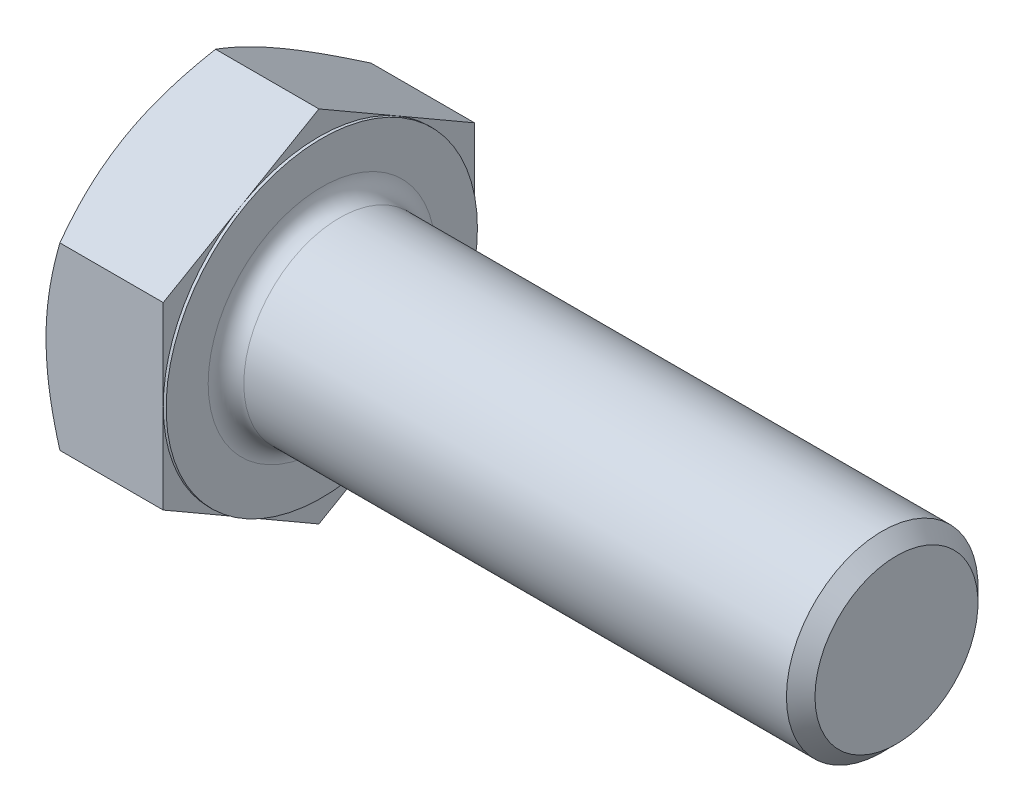
SolidWorks part; units mm, degrees
extrude "BaseHead" add sketch "Sketch1" along normal blind 15.9258
sketch "Sketch1" plane through (0, 0, 0) normal (1, 0, 0) x (0, 0, -1)
  line L0 (20.6375, 11.9151) -> (20.6375, -11.9151)
  line L1 (-20.6375, 11.9151) -> (-20.6375, -11.9151)
  line L2 (20.6375, -11.9151) -> (0, -23.8301)
  line L3 (0, -23.8301) -> (-20.6375, -11.9151)
  line L4 (20.6375, 11.9151) -> (0, 23.8301)
  line L5 (0, 23.8301) -> (-20.6375, 11.9151)
  dimension "D2" = 120
  dimension "D3" = 20.6375
  dimension "D4" = 20.6375
  dimension "D5" = 20.6375
revolve "HeadChamfer" cut sketch "Sketch3" angle 360 about L6 other way angle 60
sketch "Sketch3" plane through (0, 0, 0) normal (0, 0, 1) x (1, 0, 0)
  line L0 (0, 20.6375) -> (5.5094, 30.1801)
  line L1 (0, 23.8301) -> (0, 11.9151) construction
  line L2 (5.5094, 30.1801) -> (5.5094, 36.5301)
  line L3 (5.5094, 36.5301) -> (-12.7, 36.5301)
  line L4 (-12.7, 36.5301) -> (-12.7, 20.6375)
  line L5 (-12.7, 20.6375) -> (0, 20.6375)
  line L6 (0, 0) -> (99.06, 0) construction
  line L7 (15.9258, 23.8301) -> (0, 23.8301) construction
  dimension "D1" = 20.6375
  dimension "D2" = 6.35
  dimension "D3" = 12.7
  dimension "D4" = 6.35
  dimension "Head_ch_ang" = 30
ref_plane "Plane1" through (0, 0, 0) normal (0, 0, 1) x (1, 0, 0)
ref_plane "Plane2" through (0, 0, 0) normal (0, 1, 0) x (1, 0, 0)
ref_plane "Plane3" through (0, 0, 0) normal (1, 0, 0) x (0, 0, -1)
sketch "BodySke" plane through (0, 0, 0) normal (0, 0, 1) x (1, 0, 0)
  line L0 (0, 11.9151) -> (0, -11.9151) construction
  line L1 (0, 0) -> (92.1258, 0)
  line L2 (0, 0) -> (0, 12.7)
  line L3 (0, 12.7) -> (90.2335, 12.7)
  line L4 (92.1258, 0) -> (92.1258, 10.8077)
  line L5 (15.9258, 23.8301) -> (15.9258, 11.9151) construction
  line L6 (92.1258, 10.8077) -> (90.2335, 12.7)
  line L7 (0, 0) -> (96.52, 0) construction
  line L8 (92.1258, -10.8077) -> (90.2335, -12.7) construction
  line L9 (0, -12.7) -> (90.2335, -12.7) construction
  line L10 (18.034, 15.24) -> (18.034, -1.27) construction
  line L11 (60.3758, 15.24) -> (60.3758, -1.27) construction
  line L12 (15.9258, 11.9151) -> (15.9258, -11.9151) construction
  dimension "Diameter" = 25.4
revolve "BaseBody" add sketch "BodySke" angle 360 about L7
cosmetic thread "ThreadCosmetic" [suppressed] parameters "Thread_length"=31.75, "Thread_minor"=21.6154
sketch "Sketch4" plane through (0, 0, 0) normal (0, 0, 1) x (1, 0, 0)
  line L1 (15.9258, 23.8301) -> (15.9258, 11.9151) construction
  line L2 (15.9258, 20.6375) -> (15.5448, 20.6375)
  line L3 (15.9258, 20.6375) -> (15.9258, 49.2301)
  line L4 (15.9258, 49.2301) -> (15.5448, 49.2301)
  line L5 (0, 0) -> (95.25, 0) construction
  line L6 (0, 0) -> (96.52, 0) construction
  line L7 (15.5448, 20.6375) -> (15.5448, 49.2301)
  line L8 (15.9258, 23.8301) -> (1.8433, 23.8301) construction
  dimension "D1" = 20.6375
  dimension "D2" = 25.4
revolve "BearingFace" cut sketch "Sketch4" angle 360 about L5
fillet "HeadFillet" radius 2.3622 1 edges at (15.9258, 0, -12.7)
sketch "ThdSchSke" plane through (0, 0, 0) normal (0, 0, 1) x (1, 0, 0)
  line L0 (60.3758, -10.8077) -> (59.0508, -12.7)
  line L1 (60.3758, -10.8077) -> (61.7008, -12.7)
  line L2 (61.7008, -12.7) -> (61.7008, -15.875)
  line L3 (-3.175, 0) -> (5.1513, 0) construction
  line L5 (61.7008, -15.875) -> (59.0508, -15.875)
  line L6 (59.0508, -15.875) -> (59.0508, -12.7)
  dimension "Thread_minor" = 21.6154
  dimension "Diameter" = 25.4
  dimension "Start" = 60.3758
revolve "ThreadSchematic" [suppressed] cut sketch "ThdSchSke" angle 360 about L3
pattern_linear "ThdSchPat" [suppressed]
equation "\"D3@Sketch1\" = \"Width_flats@Sketch1\" / 2"
equation "\"D4@Sketch1\" = \"D3@Sketch1\""
equation "\"D5@Sketch1\" = \"D4@Sketch1\""
equation "\"Thread_minor@ThreadCosmetic\" = \"Minor_dia@BodySke\""
equation "\"D1@Sketch3\" = \"Width_flats@Sketch1\" / 2"
equation "\"D1@Sketch4\" = \"Width_flats@Sketch1\" / 2"
equation "\"Thread_length@ThreadCosmetic\" = ((sgn( (\"Length@BodySke\" - \"Advance@BodySke\" ) - \"Thread_nom@BodySke\" )-1)*( (\"Length@BodySke\" - \"Advance@BodySke\" ) - \"Thread_nom@BodySke\" ))/-2+ \"Thread_nom@BodySke\""
equation "\"Thread_minor@ThdSchSke\" = \"Minor_dia@BodySke\""
equation "\"Diameter@ThdSchSke\" = \"Diameter@BodySke\""
equation "\"Overcut@ThdSchSke\" = \"Diameter@BodySke\" * 1.25"
equation "\"Start@ThdSchSke\" = \"Head_ht@BaseHead\" + \"Length@BodySke\" - \"Thread_length@ThreadCosmetic\"  '---Non-countersunk---"
equation "\"Num_threads@ThdSchPat\" = int( \"Thread_length@ThreadCosmetic\" / \"Advance@BodySke\" + 0.999 )  + 1"
equation "\"Advance@ThdSchPat\" = \"Thread_length@ThreadCosmetic\" /  (\"Num_threads@ThdSchPat\" - 1) 'relax it"
equation "\"Num_threads@ThdSchPat\" = \"Num_threads@ThdSchPat\" - sgn( \"Num_threads@ThdSchPat\" - 1) '---chamfered tips only---"
